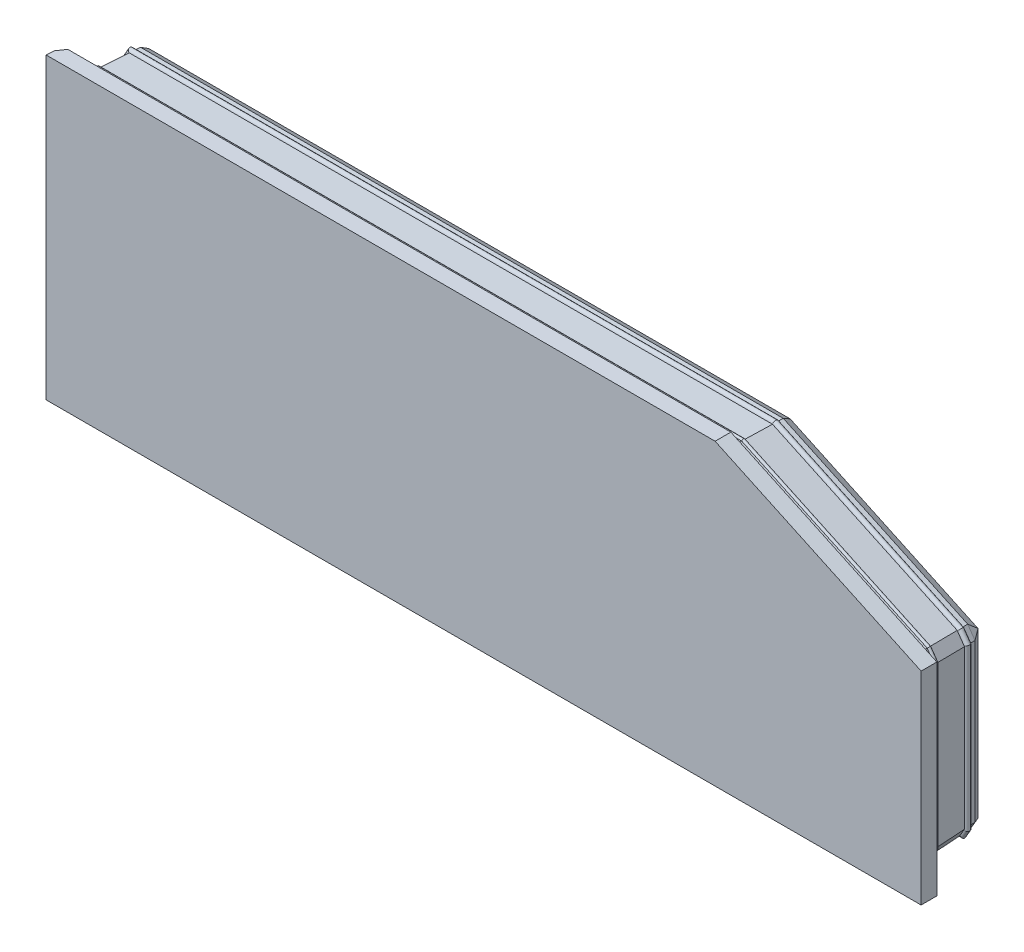
SolidWorks part; units mm, degrees
other "Markup1"
sketch "Sketch125" plane through (108.56, 0, -8) normal (1, 0, 0) x (0, 0, -1)
ref_plane "Front Plane" through (0, 0, 0) normal (0, 0, 1) x (1, 0, 0)
ref_plane "Top Plane" through (0, 0, 0) normal (0, 1, 0) x (1, 0, 0)
ref_plane "Right Plane" through (0, 0, 0) normal (1, 0, 0) x (0, 0, -1)
sketch "Sketch1" plane through (0, 0, 0) normal (0, 0, 1) x (1, 0, 0)
  line L0 (0, 0) -> (0, 37.02)
  line L1 (0, 0) -> (108.56, 0)
  line L2 (0, 37.02) -> (83.03, 37.02)
  line L3 (83.03, 37.02) -> (108.56, 25.11)
  line L4 (108.56, 25.11) -> (108.56, 0)
  dimension "D1" = 37.02
  dimension "D2" = 108.56
  dimension "D3" = 25.11
  dimension "D4" = 83.03
extrude "Boss-Extrude1" add sketch "Sketch1" along normal blind 1.95
sketch "Sketch2" plane through (0, 0, 0) normal (0, 0, -1) x (-1, 0, 0)
  line L10 (-106.53, 2.03) -> (-2.03, 2.03)
  line L11 (-2.03, 2.03) -> (-2.03, 34.99)
  line L12 (-2.03, 34.99) -> (-82.5798, 34.99)
  line L13 (-82.5798, 34.99) -> (-106.53, 23.817)
  line L14 (-106.53, 23.817) -> (-106.53, 2.03)
  line L15 (-106.53, 2.03) -> (-2.03, 2.03)
  line L16 (-2.03, 2.03) -> (-2.03, 34.99)
  line L17 (-2.03, 34.99) -> (-82.5798, 34.99)
  line L18 (-82.5798, 34.99) -> (-106.53, 23.817)
  line L19 (-106.53, 23.817) -> (-106.53, 2.03)
  dimension "D1" = 2.03
extrude "Extrude-Thin1" add sketch "Sketch2" along normal blind 8 draft 2 thin thin type one direction reverse wall 2
sketch "Sketch3" plane through (0, 37.02, 0) normal (0, 1, 0) x (1, 0, 0)
  line L6 (0, -1.95) -> (0.1, -1.95)
  line L7 (83.03, -1.95) -> (0, -1.95) construction
  line L8 (0.1, -1.95) -> (0.25, 0)
  line L9 (83.03, 0) -> (0, 0) construction
  line L10 (0.25, 0) -> (0, 0)
  line L11 (0, 0) -> (0, -1.95)
  dimension "D1" = 0.25
  dimension "D2" = 0.1
extrude "Cut-Extrude1" cut sketch "Sketch3" against normal through all
fillet "Fillet1" radius 2 10 edges at (43.0831, 32.99, 0) (4.03, 18.51, 0) (54.28, 4.03, 0) (104.53, 13.2865, 0) (93.3331, 27.7665, 0) (3.8903, 3.8903, -4) (3.8903, 33.1297, -4) (82.1672, 33.1297, -4) (104.6697, 3.8903, -4) (104.6697, 22.632, -4)
chamfer "Chamfer1" distance 1 angle 30 10 edges at (0.25, 18.51, 0) (2.3094, 18.51, -8) (42.4136, 34.7106, -8) (54.28, 2.3094, -8) (106.2506, 12.9742, -8) (94.3842, 29.1748, -8) (106.3903, 2.1697, -4) (2.1697, 2.1697, -4) (2.1697, 34.8503, -4) (106.3903, 23.728, -4)
ref_plane "Plane1" through (0, 0, -6) normal (0, 0, -1) x (-1, 0, 0)
sketch "Sketch13" plane through (0, 0, -6) normal (0, 0, -1) x (-1, 0, 0)
  line L0 (-2.6081, 34.99) -> (-82.5798, 34.99) construction
  line L1 (-2.6081, 34.99) -> (-2.03, 33.9894) construction
  line L2 (-2.03, 2.6081) -> (-2.03, 33.9894) construction
  line L3 (-2.03, 2.6081) -> (-3.0306, 2.03) construction
  line L4 (-105.9519, 2.03) -> (-3.0306, 2.03) construction
  line L5 (-105.9519, 2.03) -> (-106.53, 3.0306) construction
  line L6 (-106.53, 22.9439) -> (-106.53, 3.0306) construction
  line L7 (-82.5798, 34.99) -> (-105.6235, 24.2399) construction
  line L8 (-106.53, 22.9439) -> (-105.6235, 24.2399) construction
  line L9 (-2.6081, 34.99) -> (-82.5798, 34.99)
  line L10 (-2.6081, 34.99) -> (-2.03, 33.9894)
  line L11 (-2.03, 2.6081) -> (-2.03, 33.9894)
  line L12 (-2.03, 2.6081) -> (-3.0306, 2.03)
  line L13 (-105.9519, 2.03) -> (-3.0306, 2.03)
  line L14 (-105.9519, 2.03) -> (-106.53, 3.0306)
  line L15 (-106.53, 22.9439) -> (-106.53, 3.0306)
  line L16 (-82.5798, 34.99) -> (-105.6235, 24.2399)
  line L17 (-106.53, 22.9439) -> (-105.6235, 24.2399)
  line L18 (-2.7524, 34.74) -> (-82.5243, 34.74)
  line L19 (-82.5243, 34.74) -> (-105.4571, 24.0416)
  line L20 (-106.28, 22.8651) -> (-105.4571, 24.0416)
  line L21 (-106.28, 22.8651) -> (-106.28, 3.0976)
  line L22 (-105.8076, 2.28) -> (-106.28, 3.0976)
  line L23 (-105.8076, 2.28) -> (-3.0976, 2.28)
  line L24 (-2.28, 2.7524) -> (-3.0976, 2.28)
  line L25 (-2.28, 2.7524) -> (-2.28, 33.9224)
  line L26 (-2.7524, 34.74) -> (-2.28, 33.9224)
  dimension "D1" = 0.25
sweep "Sweep4" add path "Sketch13" circular profile diameter 0.7 parameters "D3"=0.7
ref_plane "Plane3" through (0, 0, -2) normal (0, 0, -1) x (-1, 0, 0)
sketch "Sketch37" plane through (0, 0, -2) normal (0, 0, -1) x (-1, 0, 0)
  line L18 (-3.0574, 2.13) -> (-2.13, 2.6658)
  line L19 (-2.13, 2.6658) -> (-2.13, 33.9626)
  line L20 (-2.13, 33.9626) -> (-2.6658, 34.89)
  line L21 (-105.8942, 2.13) -> (-3.0574, 2.13)
  line L22 (-106.43, 3.0574) -> (-105.8942, 2.13)
  line L23 (-106.43, 22.9124) -> (-106.43, 3.0574)
  line L24 (-105.557, 24.1606) -> (-106.43, 22.9124)
  line L25 (-82.5576, 34.89) -> (-105.557, 24.1606)
  line L26 (-2.6658, 34.89) -> (-82.5576, 34.89)
  line L27 (-3.0574, 2.13) -> (-2.13, 2.6658)
  line L28 (-2.13, 2.6658) -> (-2.13, 33.9626)
  line L29 (-2.13, 33.9626) -> (-2.6658, 34.89)
  line L30 (-105.8942, 2.13) -> (-3.0574, 2.13)
  line L31 (-106.43, 3.0574) -> (-105.8942, 2.13)
  line L32 (-106.43, 22.9124) -> (-106.43, 3.0574)
  line L33 (-105.557, 24.1606) -> (-106.43, 22.9124)
  line L34 (-82.5576, 34.89) -> (-105.557, 24.1606)
  line L35 (-2.6658, 34.89) -> (-82.5576, 34.89)
  dimension "D1" = 0.1
sweep "Sweep5" add path "Sketch37" circular profile diameter 0.4 parameters "D3"=0.4
sketch "Sketch45" plane through (0, 0, 0) normal (1, 0, 0) x (0, 0, -1)
  line L0 (0, 34.99) -> (7.9729, 34.99) construction
  line L1 (1.7091, 35.09) -> (7.005, 35.09) construction
  line L2 (6, 34.74) -> (7.7637, 34.74) construction
  line L3 (2, 34.89) -> (2.3362, 34.89) construction
  arc A0 (2.1986, 34.9132) -> (1.8035, 34.927) centre (2, 34.89) ccw construction
  circle A1 centre (6, 34.74) radius 0.35
  arc A2 (6.3489, 34.7683) -> (5.654, 34.7926) centre (6, 34.74) ccw construction
  circle A3 centre (2, 34.89) radius 0.2
  point P18 (6, 34.74)
  point P20 (7.7637, 34.74)
